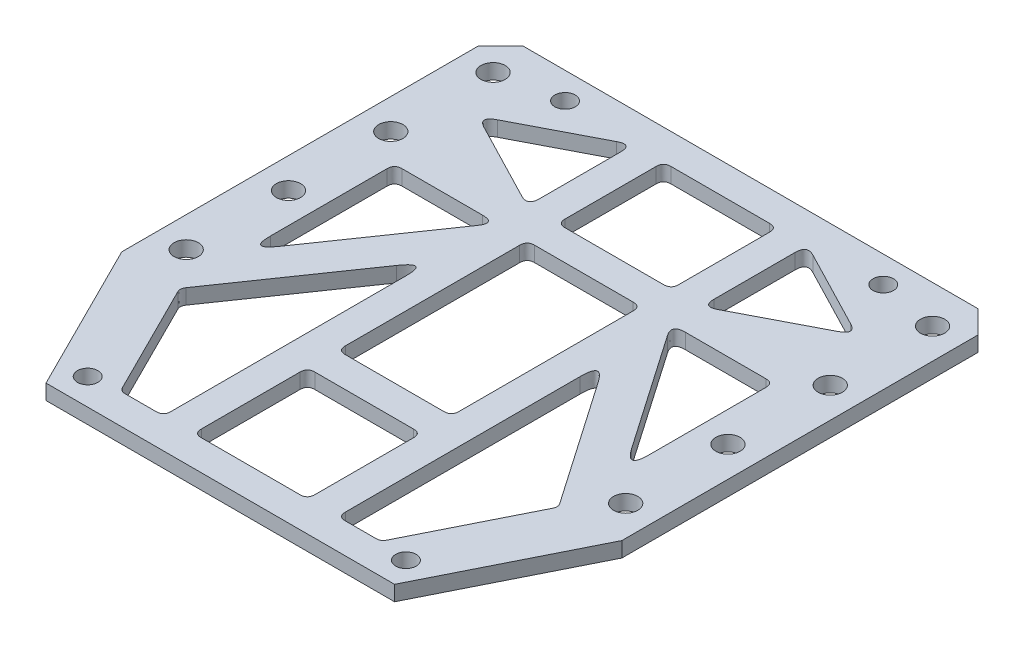
SolidWorks part; units mm, degrees
material "Thornel Mat VMA"
ref_plane "前视基准面" through (0, 0, 0) normal (0, 0, 1) x (1, 0, 0)
ref_plane "上视基准面" through (0, 0, 0) normal (0, 1, 0) x (1, 0, 0)
ref_plane "右视基准面" through (0, 0, 0) normal (1, 0, 0) x (0, 0, -1)
sketch "草图1" plane through (0, 0, 0) normal (0, 1, 0) x (1, 0, 0)
  line L0 (-29, 35) -> (-29, -35) construction
  line L1 (-21, 31.5) -> (21, 31.5) construction
  line L2 (-21, 31.5) -> (-21, -31.5) construction
  line L3 (-21, -31.5) -> (21, -31.5) construction
  line L4 (21, 31.5) -> (21, -31.5) construction
  line L5 (0, -31.5) -> (0, 31.5) construction
  line L6 (-21, 0) -> (21, 0) construction
  line L11 (-33, 35) -> (33, 35)
  line L12 (-33, 35) -> (-33, -35)
  line L13 (-33, -35) -> (33, -35)
  line L14 (33, 35) -> (33, -35)
  line L15 (0, -35) -> (0, 35) construction
  line L16 (-33, 0) -> (33, 0) construction
  line L17 (-29, 30) -> (-29, 16.5) construction
  circle A0 centre (-21, 31.5) radius 1.35
  circle A1 centre (21, 31.5) radius 1.35
  circle A2 centre (21, -31.5) radius 1.35
  circle A3 centre (-21, -31.5) radius 1.35
  circle A14 centre (-29, 30) radius 1.6
  circle A15 centre (-29, 16.5) radius 1.6
  circle A16 centre (-29, 3) radius 1.6
  circle A17 centre (-29, -10.5) radius 1.6
  circle A18 centre (29, -10.5) radius 1.6
  circle A19 centre (29, 3) radius 1.6
  circle A20 centre (29, 16.5) radius 1.6
  circle A21 centre (29, 30) radius 1.6
  point P0 (0, 0)
  point P8 (0, 1)
  point P9 (0, 0)
  point P17 (-35, 62.25)
  point P26 (-35, 48.75)
  point P29 (-35, 35.25)
  dimension "D3" = 2.7
  dimension "D7" = 3.2
  dimension "D1" = 42
  dimension "D2" = 63
  dimension "D4" = 66
  dimension "D5" = 70
  dimension "D6" = 29
  dimension "D8" = 4
  dimension "D9" = 13.5
  dimension "D10" = 5
extrude "凸台-拉伸1" add sketch "草图1" along normal blind 2
sketch "草图2" plane through (0, 2, 0) normal (0, 1, 0) x (1, 0, 0)
  line L0 (0, 35) -> (0, -49965) construction
  line L1 (33, 35) -> (-33, 35) construction
  line L2 (-33, -15) -> (-33, -35)
  line L3 (-33, 35) -> (-33, -35) construction
  line L4 (-33, -35) -> (-23, -35)
  line L5 (-33, -35) -> (33, -35) construction
  line L6 (-23, -35) -> (-33, -15)
  line L7 (33, -35) -> (23, -35)
  line L8 (33, -15) -> (33, -35)
  line L9 (23, -35) -> (33, -15)
  line L10 (-11.5, 4.2011) -> (-11.5, -31)
  line L15 (-7.5, -16) -> (7.5, -16)
  line L16 (-7.5, -16) -> (-7.5, -31)
  line L17 (-7.5, -31) -> (7.5, -31)
  line L18 (7.5, -16) -> (7.5, -31)
  line L19 (0, -31) -> (0, -16) construction
  line L20 (-7.5, -23.5) -> (7.5, -23.5) construction
  line L21 (-7.5, 13) -> (7.5, 13)
  line L22 (-7.5, 13) -> (-7.5, -12)
  line L23 (-7.5, -12) -> (7.5, -12)
  line L24 (7.5, 13) -> (7.5, -12)
  line L25 (0, -12) -> (0, 13) construction
  line L26 (-7.5, 0.5) -> (7.5, 0.5) construction
  line L27 (-7.5, 31) -> (7.5, 31)
  line L28 (-7.5, 31) -> (-7.5, 17)
  line L29 (-7.5, 17) -> (7.5, 17)
  line L30 (7.5, 31) -> (7.5, 17)
  line L31 (0, 17) -> (0, 31) construction
  line L32 (-7.5, 24) -> (7.5, 24) construction
  line L34 (-25, -15.3475) -> (-11.5, 4.2011)
  line L35 (-11.5, 13) -> (-25, -6.5486)
  line L36 (-25, -6.5486) -> (-25, 13)
  line L37 (-25, 13) -> (-11.5, 13)
  line L38 (-11.5, 31) -> (-11.5, 17)
  line L39 (-11.5, 31) -> (-25, 24)
  line L40 (-25, 24) -> (-11.5, 17)
  line L41 (-11.5, -31) -> (-17.1738, -31)
  line L42 (-17.1738, -31) -> (-25, -15.3475)
  line L43 (11.5, -31) -> (17.1738, -31)
  line L44 (11.5, 4.2011) -> (11.5, -31)
  line L45 (25, -15.3475) -> (11.5, 4.2011)
  line L46 (17.1738, -31) -> (25, -15.3475)
  line L47 (25, -6.5486) -> (25, 13)
  line L48 (11.5, 13) -> (25, -6.5486)
  line L49 (25, 13) -> (11.5, 13)
  line L50 (11.5, 31) -> (25, 24)
  line L51 (11.5, 31) -> (11.5, 17)
  line L52 (25, 24) -> (11.5, 17)
  point P4 (0, 35)
  point P16 (0, -23.5)
  point P20 (0, 0.5)
  point P24 (0, 24)
  dimension "D1" = 20
  dimension "D2" = 10
  dimension "D3" = 15
  dimension "D4" = 15
  dimension "D5" = 4
  dimension "D6" = 25
  dimension "D7" = 4
  dimension "D8" = 4
  dimension "D9" = 4
  dimension "D10" = 8
  dimension "4" = 4
  dimension "D11" = 7
  dimension "5" = 5
extrude "切除-拉伸1" cut sketch "草图2" against normal through all
chamfer "倒角1" distance 3 angle 45 2 edges at (33, 1, -35) (-33, 1, -35)
fillet "圆角1" radius 1 32 edges at (-11.5, 1, 31) (-25, 1, 15.3475) (-17.1738, 1, 31) (-11.5, 1, -4.2011) (-25, 1, 6.5486) (-11.5, 1, -13) (-25, 1, -13) (-11.5, 1, -17) (-11.5, 1, -31) (-25, 1, -24) (25, 1, 15.3475) (17.1738, 1, 31) (11.5, 1, 31) (11.5, 1, -4.2011) (25, 1, -13) (25, 1, 6.5486) (11.5, 1, -13) (25, 1, -24) (11.5, 1, -17) (11.5, 1, -31) (7.5, 1, -31) (7.5, 1, -17) (-7.5, 1, -31) (-7.5, 1, -17) (-7.5, 1, -13) (7.5, 1, -13) (-7.5, 1, 12) (7.5, 1, 12) (7.5, 1, 16) (7.5, 1, 31) (-7.5, 1, 31) (-7.5, 1, 16) conic rho 0.5
